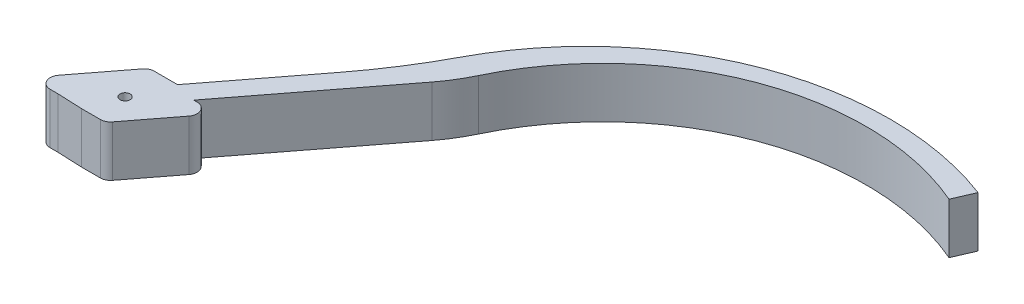
SolidWorks part; units mm, degrees
ref_plane "Front Plane" through (0, 0, 0) normal (0, 0, 1) x (1, 0, 0)
ref_plane "Top Plane" through (0, 0, 0) normal (0, 1, 0) x (1, 0, 0)
ref_plane "Right Plane" through (0, 0, 0) normal (1, 0, 0) x (0, 0, -1)
sketch "Sketch1" plane through (0, 0, 0) normal (0, 1, 0) x (1, 0, 0)
  line L4 (47.7948, 18.9954) -> (48.8939, 21.5354)
  line L5 (0, 0) -> (-12.9802, -16.9114)
  line L7 (-19.4955, -25.4) -> (-16.395, -25.5322)
  line L8 (4.122, 1.1987) -> (-10.2896, -17.5776)
  line L9 (-19.4955, -25.4) -> (-23.0335, -25.4)
  line L11 (-23.0335, -25.4) -> (-16.5182, -16.9114)
  line L12 (-12.9802, -16.9114) -> (-16.5182, -16.9114)
  line L13 (-16.395, -25.5322) -> (-13.4, -25.5322)
  line L15 (-13.4, -25.5322) -> (-7.2946, -17.5776)
  line L16 (-10.2896, -17.5776) -> (-7.2946, -17.5776)
  arc A1 (4.122, 1.1987) -> (47.7948, 18.9954) centre (34.6814, -11.309) cw
  arc A2 (0, 0) -> (48.8939, 21.5354) centre (35.3973, -14.0939) cw
  circle A3 centre (-14.9451, -21.5234) radius 0.635
  dimension "D1" = 33.02
  dimension "D5" = 38.1
  dimension "D6" = 1.27
  dimension "D2" = 2.54
  dimension "D3" = 2.54
  dimension "D4" = 25.4
extrude "Boss-Extrude2" add sketch "Sketch1" along normal blind 6.35
fillet "Fillet3" radius 20.32 1 edges at (4.122, 3.175, -1.1987)
fillet "Fillet4" radius 66.04 1 edges at (0, 3.175, 0)
fillet "Fillet5" radius 1.27 4 edges at (-16.5182, 3.175, 16.9114) (-23.0335, 3.175, 25.4) (-7.2946, 3.175, 17.5776) (-13.4, 3.175, 25.5322)
